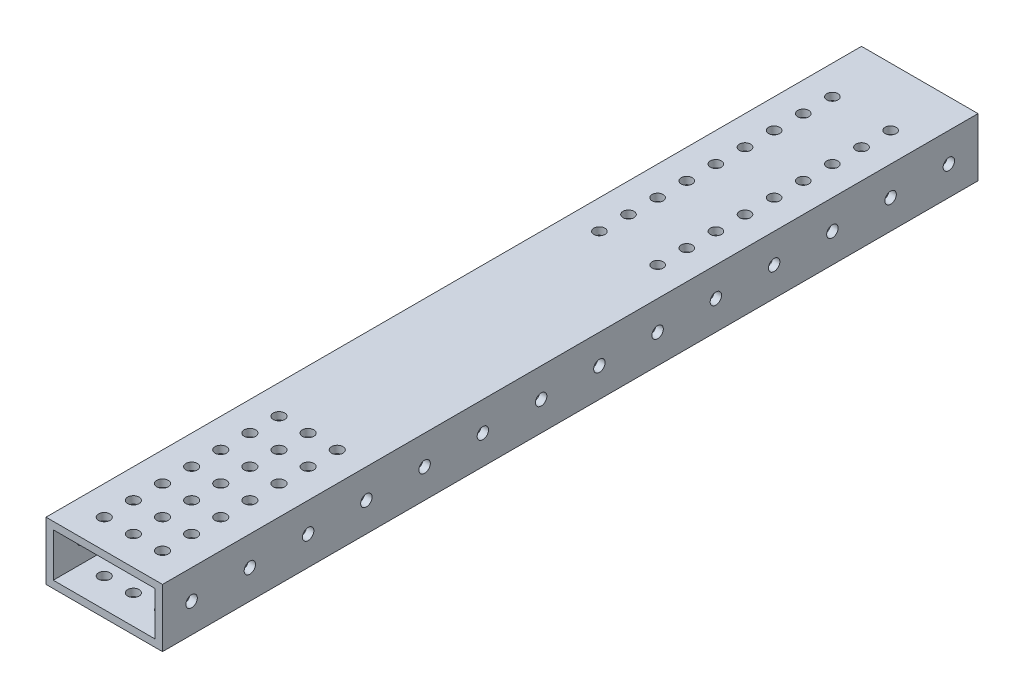
SolidWorks part; units mm, degrees
material "6061-T6 (SS)"
ref_plane "Front Plane" through (0, 0, 0) normal (0, 0, 1) x (1, 0, 0)
ref_plane "Top Plane" through (0, 0, 0) normal (0, 1, 0) x (1, 0, 0)
ref_plane "Right Plane" through (0, 0, 0) normal (1, 0, 0) x (0, 0, -1)
sketch "Sketch1" plane through (0, 0, 0) normal (0, 0, 1) x (1, 0, 0)
  line L0 (-22.225, 9.525) -> (22.225, 9.525)
  line L1 (-25.4, 12.7) -> (25.4, 12.7)
  line L2 (-25.4, 12.7) -> (-25.4, -12.7)
  line L3 (-25.4, -12.7) -> (25.4, -12.7)
  line L4 (25.4, 12.7) -> (25.4, -12.7)
  line L5 (22.225, 9.525) -> (22.225, -9.525)
  line L6 (-22.225, -9.525) -> (22.225, -9.525)
  line L7 (-22.225, 9.525) -> (-22.225, -9.525)
  line L8 (-25.4, 12.7) -> (25.4, -12.7) construction
  line L9 (25.4, 12.7) -> (-25.4, -12.7) construction
  point P5 (0, 0)
  dimension "D1" = 50.8
  dimension "D2" = 25.4
  dimension "D3" = 3.175
extrude "Boss-Extrude1" add sketch "Sketch1" along normal mid plane 355.6
sketch "Sketch2" plane through (0, -12.7, 0) normal (0, -1, 0) x (1, 0, 0)
  circle A0 centre (12.7, -63.5) radius 2.413 construction
  circle A1 centre (12.7, -76.2) radius 2.413 construction
  circle A2 centre (12.7, -88.9) radius 2.413 construction
  circle A3 centre (12.7, -101.6) radius 2.413 construction
  circle A4 centre (12.7, -114.3) radius 2.413 construction
  circle A5 centre (12.7, -127) radius 2.413 construction
  circle A6 centre (12.7, -139.7) radius 2.413 construction
  circle A7 centre (12.7, -152.4) radius 2.413 construction
  circle A8 centre (-12.7, -152.4) radius 2.413 construction
  circle A9 centre (-12.7, -139.7) radius 2.413 construction
  circle A10 centre (-12.7, -127) radius 2.413 construction
  circle A11 centre (-12.7, -114.3) radius 2.413 construction
  circle A12 centre (-12.7, -101.6) radius 2.413 construction
  circle A13 centre (-12.7, -88.9) radius 2.413 construction
  circle A14 centre (-12.7, -76.2) radius 2.413 construction
  circle A15 centre (-12.7, -63.5) radius 2.413 construction
  circle A16 centre (-12.7, -50.8) radius 2.413 construction
  circle A17 centre (12.7, -50.8) radius 2.413 construction
  circle A18 centre (12.7, -63.5) radius 2.413
  circle A19 centre (12.7, -76.2) radius 2.413
  circle A20 centre (12.7, -88.9) radius 2.413
  circle A21 centre (12.7, -101.6) radius 2.413
  circle A22 centre (12.7, -114.3) radius 2.413
  circle A23 centre (12.7, -127) radius 2.413
  circle A24 centre (12.7, -139.7) radius 2.413
  circle A25 centre (12.7, -152.4) radius 2.413
  circle A26 centre (-12.7, -152.4) radius 2.413
  circle A27 centre (-12.7, -139.7) radius 2.413
  circle A28 centre (-12.7, -127) radius 2.413
  circle A29 centre (-12.7, -114.3) radius 2.413
  circle A30 centre (-12.7, -101.6) radius 2.413
  circle A31 centre (-12.7, -88.9) radius 2.413
  circle A32 centre (-12.7, -76.2) radius 2.413
  circle A33 centre (-12.7, -63.5) radius 2.413
  circle A34 centre (-12.7, -50.8) radius 2.413
  circle A35 centre (12.7, -50.8) radius 2.413
  circle A36 centre (-12.7, 165.1) radius 2.4892 construction
  circle A37 centre (-12.7, 152.4) radius 2.4892 construction
  circle A38 centre (-12.7, 139.7) radius 2.4892 construction
  circle A39 centre (-12.7, 127) radius 2.4892 construction
  circle A40 centre (-12.7, 114.3) radius 2.4892 construction
  circle A41 centre (-12.7, 101.6) radius 2.4892 construction
  circle A42 centre (-12.7, 88.9) radius 2.4892 construction
  circle A43 centre (0, 88.9) radius 2.4892 construction
  circle A44 centre (0, 101.6) radius 2.4892 construction
  circle A45 centre (0, 114.3) radius 2.4892 construction
  circle A46 centre (0, 127) radius 2.4892 construction
  circle A47 centre (0, 139.7) radius 2.4892 construction
  circle A48 centre (0, 152.4) radius 2.4892 construction
  circle A49 centre (0, 165.1) radius 2.4892 construction
  circle A50 centre (12.7, 165.1) radius 2.4892 construction
  circle A51 centre (12.7, 152.4) radius 2.4892 construction
  circle A52 centre (12.7, 139.7) radius 2.4892 construction
  circle A53 centre (12.7, 127) radius 2.4892 construction
  circle A54 centre (12.7, 114.3) radius 2.4892 construction
  circle A55 centre (12.7, 101.6) radius 2.4892 construction
  circle A56 centre (12.7, 88.9) radius 2.4892 construction
  circle A57 centre (-12.7, 165.1) radius 2.4892
  circle A58 centre (-12.7, 152.4) radius 2.4892
  circle A59 centre (-12.7, 139.7) radius 2.4892
  circle A60 centre (-12.7, 127) radius 2.4892
  circle A61 centre (-12.7, 114.3) radius 2.4892
  circle A62 centre (-12.7, 101.6) radius 2.4892
  circle A63 centre (-12.7, 88.9) radius 2.4892
  circle A64 centre (0, 88.9) radius 2.4892
  circle A65 centre (0, 101.6) radius 2.4892
  circle A66 centre (0, 114.3) radius 2.4892
  circle A67 centre (0, 127) radius 2.4892
  circle A68 centre (0, 139.7) radius 2.4892
  circle A69 centre (0, 152.4) radius 2.4892
  circle A70 centre (0, 165.1) radius 2.4892
  circle A71 centre (12.7, 165.1) radius 2.4892
  circle A72 centre (12.7, 152.4) radius 2.4892
  circle A73 centre (12.7, 139.7) radius 2.4892
  circle A74 centre (12.7, 127) radius 2.4892
  circle A75 centre (12.7, 114.3) radius 2.4892
  circle A76 centre (12.7, 101.6) radius 2.4892
  circle A77 centre (12.7, 88.9) radius 2.4892
extrude "Cut-Extrude1" cut sketch "Sketch2" against normal through all
sketch "Sketch3" plane through (25.4, 0, 0) normal (1, 0, 0) x (0, 0, -1)
  line L0 (-177.8, 0) -> (177.8, 0) construction
  line L1 (-177.8, -12.7) -> (-177.8, 12.7) construction
  line L2 (177.8, -12.7) -> (177.8, 12.7) construction
  circle A0 centre (-165.1, 0) radius 2.4892
  circle A1 centre (-139.7, 0) radius 2.4892
  circle A2 centre (-114.3, 0) radius 2.4892
  circle A3 centre (-88.9, 0) radius 2.4892
  circle A4 centre (-63.5, 0) radius 2.4892
  circle A5 centre (-38.1, 0) radius 2.4892
  circle A6 centre (-12.7, 0) radius 2.4892
  circle A7 centre (12.7, 0) radius 2.4892
  circle A8 centre (38.1, 0) radius 2.4892
  circle A9 centre (63.5, 0) radius 2.4892
  circle A10 centre (88.9, 0) radius 2.4892
  circle A11 centre (114.3, 0) radius 2.4892
  circle A12 centre (139.7, 0) radius 2.4892
  circle A13 centre (165.1, 0) radius 2.4892
  dimension "D1" = 4.9784
  dimension "D2" = 12.7
  dimension "D4" = 25.4
  dimension "D3" = 14
extrude "Cut-Extrude2" cut sketch "Sketch3" against normal through all
